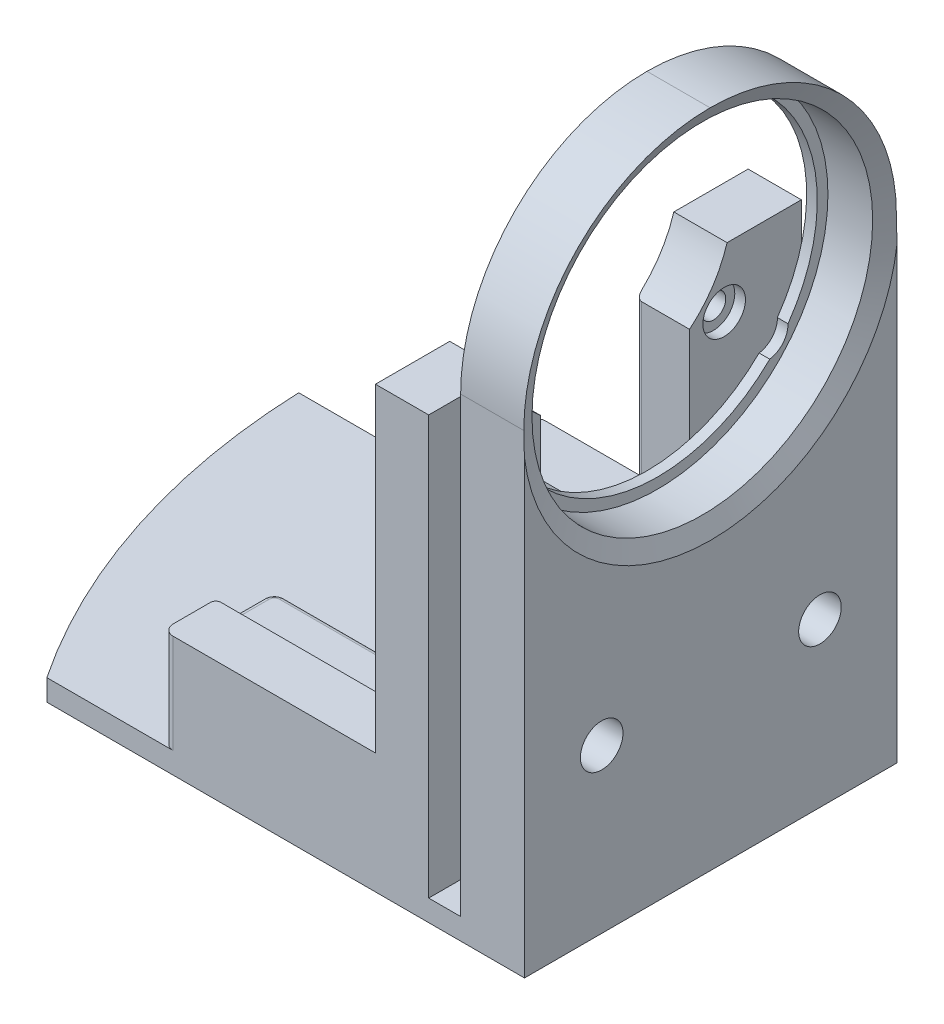
SolidWorks part; units mm, degrees
ref_plane "정면" through (0, 0, 0) normal (0, 0, 1) x (1, 0, 0)
ref_plane "윗면" through (0, 0, 0) normal (0, 1, 0) x (1, 0, 0)
ref_plane "우측면" through (0, 0, 0) normal (1, 0, 0) x (0, 0, -1)
sketch "스케치1" plane through (0, 0, 0) normal (0, 1, 0) x (1, 0, 0)
  line L1 (-11.2427, -2.5271) -> (-67.4527, -2.5271)
  line L2 (-11.2427, -2.5271) -> (-11.2427, -66.5571)
  arc A0 (-67.4527, -2.5271) -> (-11.2427, -66.5571) centre (0, 0) ccw
  dimension "D1" = 135
  dimension "D2" = 56.21
  dimension "D3" = 64.03
extrude "보스-돌출1" add sketch "스케치1" along normal blind 2 contours L1 A0 L2 region at (-34.5712, 0, 28.7061)
sketch "스케치2" plane through (0, 2, 0) normal (0, 1, 0) x (1, 0, 0)
  line L1 (-11.2427, -2.5271) -> (-17.2427, -2.5271)
  line L2 (-11.2427, -2.5271) -> (-11.2427, -37.5271)
  line L3 (-11.2427, -37.5271) -> (-17.2427, -37.5271)
  line L4 (-17.2427, -2.5271) -> (-17.2427, -37.5271)
  dimension "D1" = 35
  dimension "D2" = 6
extrude "보스-돌출2" add sketch "스케치2" along normal blind 60
fillet "필렛1" radius 17.5 2 edges at (-14.2427, 62, 2.5271) (-14.2427, 62, 37.5271)
sketch "스케치3" plane through (-11.2427, 0, 0) normal (1, 0, 0) x (0, 0, -1)
  circle A0 centre (-20.0271, 44.5) radius 16
  dimension "D1" = 32
extrude "컷-돌출1" cut sketch "스케치3" against normal blind 5
chamfer "모따기1" distance 0.8 angle 64 1 edges at (-11.2427, 44.5, 4.0271) first distance on face at (-16.2427, 44.5, 4.0271)
sketch "스케치4" plane through (-16.2427, 0, 0) normal (1, 0, 0) x (0, 0, -1)
  circle A0 centre (-20.0271, 44.5) radius 15
  circle A1 centre (-20.0271, 44.5) radius 16 construction
  dimension "D1" = 1
extrude "컷-돌출2" cut sketch "스케치4" against normal through all
sketch "스케치5" plane through (0, 2, 0) normal (0, 1, 0) x (1, 0, 0)
  line L0 (-17.2427, -2.5271) -> (-67.4527, -2.5271) construction
  line L1 (-20.2427, -2.5271) -> (-45.2427, -2.5271)
  line L2 (-20.2427, -2.5271) -> (-20.2427, -13.0271)
  line L3 (-20.2427, -13.0271) -> (-45.2427, -13.0271)
  line L4 (-45.2427, -2.5271) -> (-45.2427, -13.0271)
  line L5 (-17.2427, -2.5271) -> (-17.2427, -37.5271) construction
  line L6 (-20.2427, -27.0271) -> (-45.2427, -27.0271)
  line L7 (-20.2427, -27.0271) -> (-20.2427, -37.5271)
  line L8 (-20.2427, -37.5271) -> (-45.2427, -37.5271)
  line L9 (-45.2427, -27.0271) -> (-45.2427, -37.5271)
  dimension "D1" = 10.5
  dimension "D2" = 25
  dimension "D3" = 35
  dimension "D4" = 3
extrude "보스-돌출3" add sketch "스케치5" along normal blind 7.3
sketch "스케치6" plane through (0, 9.3, 0) normal (0, 1, 0) x (1, 0, 0)
  line L0 (-45.2427, -32.5271) -> (-25.2427, -32.5271)
  line L1 (-45.2427, -2.5271) -> (-20.2427, -2.5271)
  line L2 (-45.2427, -2.5271) -> (-45.2427, -7.5271)
  line L3 (-25.2427, -13.0271) -> (-20.2427, -13.0271)
  line L4 (-20.2427, -2.5271) -> (-20.2427, -13.0271)
  line L5 (-45.2427, -37.5271) -> (-20.2427, -37.5271)
  line L6 (-45.2427, -37.5271) -> (-45.2427, -32.5271)
  line L7 (-25.2427, -27.0271) -> (-20.2427, -27.0271)
  line L8 (-20.2427, -37.5271) -> (-20.2427, -27.0271)
  line L9 (-45.2427, -7.5271) -> (-25.2427, -7.5271)
  line L10 (-25.2427, -7.5271) -> (-25.2427, -13.0271)
  line L11 (-25.2427, -32.5271) -> (-25.2427, -27.0271)
  line L12 (-45.2427, -13.0271) -> (-20.2427, -13.0271) construction
  line L13 (-45.2427, -27.0271) -> (-20.2427, -27.0271) construction
  line L14 (-25.2427, -37.5271) -> (-25.2427, -27.0271) construction
  line L15 (-45.2427, -32.5271) -> (-20.2427, -32.5271) construction
  line L16 (-25.2427, -2.5271) -> (-25.2427, -13.0271) construction
  line L17 (-45.2427, -7.5271) -> (-20.2427, -7.5271) construction
  dimension "D1" = 5.5
  dimension "D2" = 5.5
  dimension "D3" = 5
  dimension "D4" = 5
extrude "보스-돌출4" add sketch "스케치6" along normal blind 2
fillet "필렛2" radius 1 4 edges at (-45.2427, 6.65, 37.5271) (-45.2427, 5.65, 27.0271) (-45.2427, 5.65, 13.0271) (-45.2427, 6.65, 2.5271)
sketch "스케치7" plane through (-25.2427, 0, 0) normal (-1, 0, 0) x (0, 0, 1)
  line L0 (13.0271, 9.3) -> (13.0271, 2) construction
  line L1 (2.5271, 11.3) -> (13.0271, 11.3)
  line L2 (2.5271, 11.3) -> (2.5271, 41.3)
  line L3 (2.5271, 41.3) -> (9.5029, 41.3)
  line L4 (13.0271, 11.3) -> (13.0271, 36.0147)
  line L5 (37.5271, 11.3) -> (27.0271, 11.3)
  line L6 (37.5271, 11.3) -> (37.5271, 41.3)
  line L7 (37.5271, 41.3) -> (30.5514, 41.3)
  line L8 (27.0271, 11.3) -> (27.0271, 36.0147)
  arc A0 (27.0271, 36.0147) -> (30.5514, 41.3) centre (20.0271, 44.5) ccw
  arc A1 (9.5029, 41.3) -> (13.0271, 36.0147) centre (20.0271, 44.5) ccw
  dimension "D2" = 22
  dimension "D1" = 30
extrude "보스-돌출5" add sketch "스케치7" against normal blind 5
sketch "스케치9" plane through (-25.2427, 0, 0) normal (-1, 0, 0) x (0, 0, 1)
  line L0 (7.5271, 9.3) -> (13.0271, 9.3) construction
  line L1 (9.7771, 35.8) -> (30.2771, 35.8) construction
  line L2 (9.7771, 35.8) -> (9.7771, 15.3) construction
  line L3 (9.7771, 15.3) -> (30.2771, 15.3) construction
  line L4 (30.2771, 35.8) -> (30.2771, 15.3) construction
  circle A0 centre (20.0271, 44.5) radius 15 construction
  circle A1 centre (9.7771, 35.8) radius 1.15
  circle A2 centre (9.7771, 15.3) radius 1.15
  circle A3 centre (30.2771, 15.3) radius 1.15
  circle A4 centre (30.2771, 35.8) radius 1.15
  dimension "D4" = 10.25
  dimension "D5" = 2.3
  dimension "D1" = 20.5
  dimension "D2" = 20.5
  dimension "D3" = 6
extrude "컷-돌출3" cut sketch "스케치9" against normal through all
sketch "스케치10" plane through (-11.2427, 0, 0) normal (1, 0, 0) x (0, 0, -1)
  circle A0 centre (-30.2771, 15.3) radius 2
  circle A1 centre (-9.7771, 15.3) radius 2
  circle A2 centre (-9.7771, 35.8) radius 2
  circle A3 centre (-30.2771, 35.8) radius 2
  dimension "D1" = 4
extrude "컷-돌출4" cut sketch "스케치10" against normal blind 10
fillet "필렛3" radius 0.5 12 edges at (-45.2427, 10.3, 7.5271) (-45.2427, 10.3, 32.5271) (-34.7427, 9.3, 13.0271) (-44.9498, 9.3, 12.7342) (-34.7427, 9.3, 27.0271) (-44.9498, 9.3, 27.32) (-45.2427, 9.3, 9.7771) (-45.2427, 9.3, 30.2771) (-35.2427, 9.3, 32.5271) (-35.2427, 9.3, 7.5271) (-25.2427, 22.6574, 27.0271) (-25.2427, 22.6574, 13.0271)
sketch "스케치12" plane through (0, 2, 0) normal (0, 1, 0) x (1, 0, 0)
  line L0 (-11.2427, -37.5271) -> (-11.2427, -66.5571)
  line L1 (-11.2427, -66.5571) -> (-67.4527, -66.5571)
  line L2 (-67.4527, -66.5571) -> (-67.4527, -37.5271)
  line L3 (-67.4527, -37.5271) -> (-11.2427, -37.5271)
extrude "컷-돌출5" cut sketch "스케치12" against normal through all
